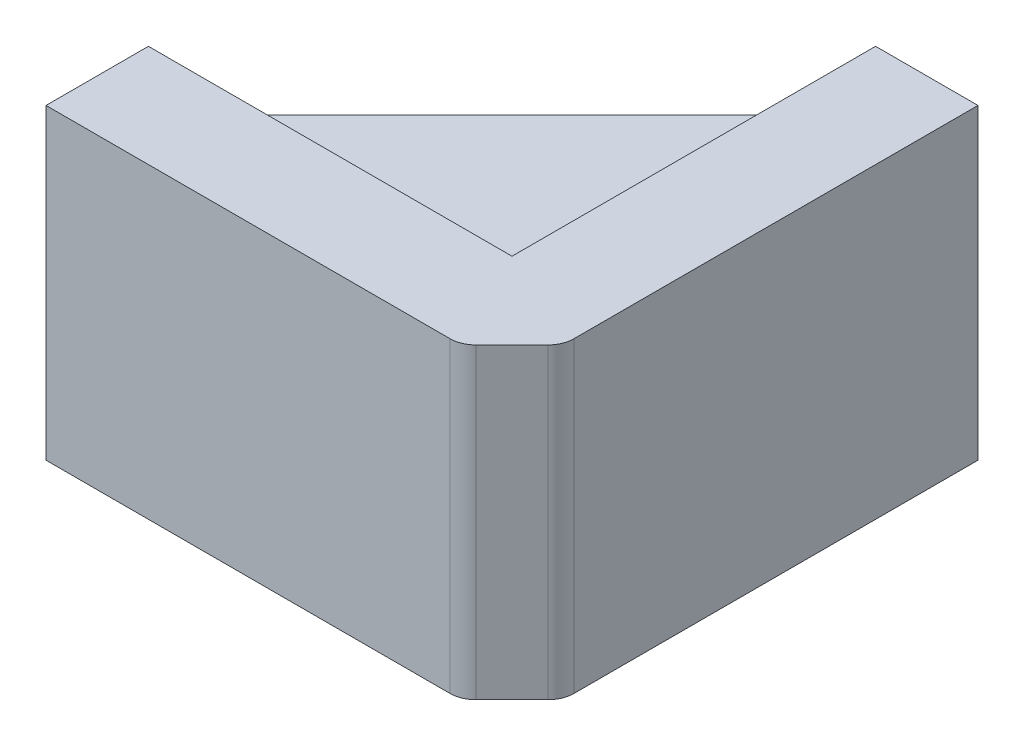
SolidWorks part; units mm, degrees
material "ABS"
ref_plane "Alzado" through (0, 0, 0) normal (0, 0, 1) x (1, 0, 0)
ref_plane "Planta" through (0, 0, 0) normal (0, 1, 0) x (1, 0, 0)
ref_plane "Vista lateral" through (0, 0, 0) normal (1, 0, 0) x (0, 0, -1)
sketch "Sketch1" plane through (0, 0, 0) normal (0, 1, 0) x (1, 0, 0)
  line L0 (25.5, 45.5) -> (25.5, -25.5)
  line L1 (-45.5, -45.5) -> (45.5, -45.5)
  line L2 (-45.5, -45.5) -> (-45.5, 45.5) construction
  line L3 (-45.5, 45.5) -> (45.5, 45.5) construction
  line L4 (45.5, -45.5) -> (45.5, 45.5)
  line L5 (-45.5, -45.5) -> (45.5, 45.5) construction
  line L6 (-45.5, 45.5) -> (45.5, -45.5) construction
  line L7 (25.5, -25.5) -> (-45.5, -25.5)
  line L8 (-45.5, -25.5) -> (-45.5, -45.5)
  line L9 (25.5, 45.5) -> (45.5, 45.5)
  point P0 (0, 0)
  dimension "D1" = 71
  dimension "D3" = 20
extrude "Boss-Extrude1" add sketch "Sketch1" along normal blind 60
chamfer "Chamfer1" distance 10 angle 45 1 edges at (45.5, 30, 45.5)
fillet "Fillet1" radius 5 2 edges at (45.5, 30, 35.5) (35.5, 30, 45.5)
sketch "Sketch2" plane through (0, 60, 0) normal (0, 1, 0) x (1, 0, 0)
  line L0 (25.5, 31.0685) -> (-31.0685, -25.5)
  line L1 (25.5, 45.5) -> (25.5, -25.5) construction
  line L2 (25.5, -25.5) -> (-45.5, -25.5) construction
  line L3 (-31.0685, -25.5) -> (25.5, -25.5)
  line L4 (25.5, -25.5) -> (25.5, 31.0685)
  line L5 (36.9645, -44.0355) -> (44.0355, -36.9645) construction
  dimension "D1" = 40
extrude "Boss-Extrude2" add sketch "Sketch2" against normal blind 5 from offset 4.4 offset against normal yes
